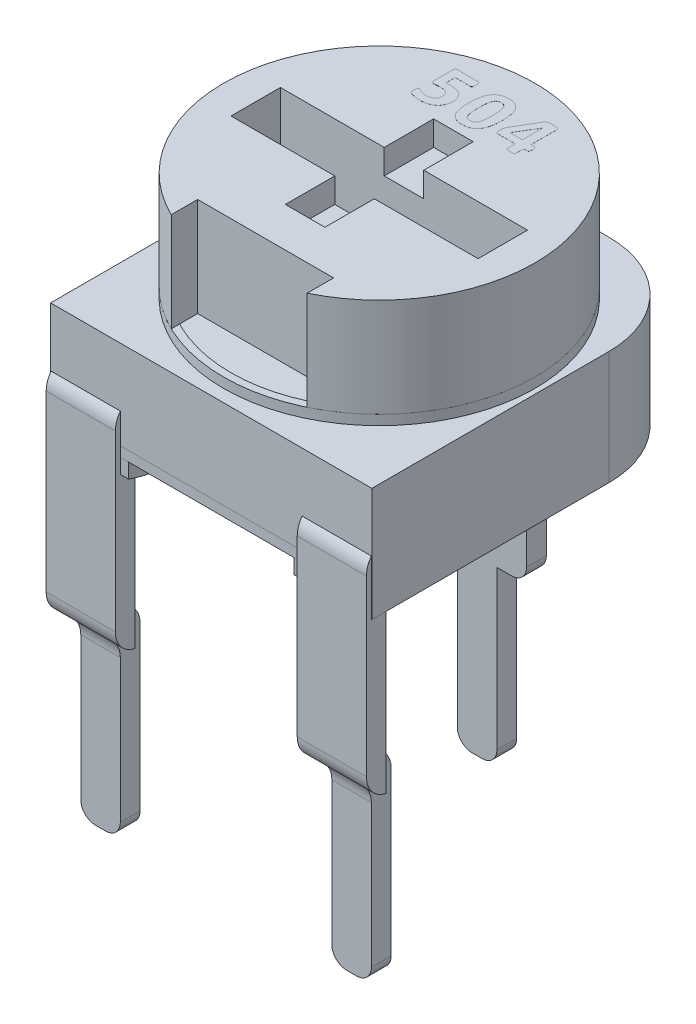
SolidWorks part; units mm, degrees
material "ABS"
ref_plane "Front Plane" through (0, 0, 0) normal (0, 0, 1) x (1, 0, 0)
ref_plane "Top Plane" through (0, 0, 0) normal (0, 1, 0) x (1, 0, 0)
ref_plane "Right Plane" through (0, 0, 0) normal (1, 0, 0) x (0, 0, -1)
sketch "Sketch1" plane through (0, 0, 0) normal (0, 1, 0) x (1, 0, 0)
  line L0 (0, 3.15) -> (0, -3.15) construction
  line L1 (0, 3.15) -> (0, 3.4) construction
  line L2 (0, -3.15) -> (0, -3.4) construction
  line L3 (-3.15, 0) -> (3.15, 0) construction
  line L4 (3.15, 0) -> (3.25, 0) construction
  line L5 (-3.15, 0) -> (-3.25, 0) construction
  line L6 (-3.25, -3.4) -> (3.25, -3.4)
  line L7 (-3.25, -3.4) -> (-3.25, 3.4)
  line L8 (-3.25, 3.4) -> (3.25, 3.4)
  line L9 (3.25, 3.4) -> (3.25, -3.4)
  circle A0 centre (0, 0) radius 3.15 construction
  dimension "D1" = 6.3
  dimension "D2" = 6.8
  dimension "D3" = 6.5
extrude "Boss-Extrude1" add sketch "Sketch1" along normal blind 2.3
sketch "Sketch2" plane through (0, 2.3, 0) normal (0, 1, 0) x (1, 0, 0)
  circle A0 centre (0, 0) radius 3.15 construction
  circle A1 centre (0, 0) radius 3.15
extrude "Boss-Extrude2" add sketch "Sketch2" along normal blind 0.2
fillet "Fillet1" radius 2 2 edges at (3.25, 1.15, -3.4) (-3.25, 1.15, -3.4)
sketch "Sketch3" plane through (0, 0, 0) normal (0, -1, 0) x (1, 0, 0)
  line L0 (0, 0) -> (0, -2.5) construction
  line L1 (-1.75, -2.5) -> (1.75, -2.5)
  line L6 (-2.25, -2) -> (-2.25, 2)
  line L7 (2.25, -2) -> (2.25, 2)
  line L8 (-2.25, 2) -> (-3, 2)
  line L9 (-3, 2) -> (-3, 3.4)
  line L10 (-3.25, 3.4) -> (3.25, 3.4) construction
  line L11 (2.25, 2) -> (3, 2)
  line L12 (3, 2) -> (3, 3.4)
  line L13 (3, 3.4) -> (-3, 3.4)
  line L14 (0, 0) -> (0, 3.4) construction
  arc A0 (-1.75, -2.5) -> (-2.25, -2) centre (-1.75, -2) cw
  arc A1 (1.75, -2.5) -> (2.25, -2) centre (1.75, -2) ccw
  point P20 (2.25, -2.5)
  dimension "D6" = 0.5
  dimension "D1" = 4.5
  dimension "D2" = 2.5
  dimension "D3" = 4.5
  dimension "D4" = 1.4
  dimension "D5" = 6
extrude "Cut-Extrude1" cut sketch "Sketch3" against normal blind 0.5
sketch "Sketch4" plane through (0, 0.5, 0) normal (0, -1, 0) x (1, 0, 0)
  line L8 (-3, 2) -> (-2.25, 2)
  line L9 (-2.25, 2) -> (-2.25, -2)
  line L10 (-1.75, -2.5) -> (1.75, -2.5)
  line L11 (2.25, -2) -> (2.25, 2)
  line L12 (2.25, 2) -> (3, 2)
  line L13 (3, 2) -> (3, 3.4)
  line L14 (3, 3.4) -> (-3, 3.4)
  line L15 (-3, 3.4) -> (-3, 2)
  line L16 (-3, 2) -> (-2.25, 2)
  line L17 (-2.25, 2) -> (-2.25, -2)
  line L18 (-1.75, -2.5) -> (1.75, -2.5)
  line L19 (2.25, -2) -> (2.25, 2)
  line L20 (2.25, 2) -> (3, 2)
  line L21 (3, 2) -> (3, 3.4)
  line L22 (3, 3.4) -> (-3, 3.4)
  line L23 (-3, 3.4) -> (-3, 2)
  arc A2 (-2.25, -2) -> (-1.75, -2.5) centre (-1.75, -2) ccw
  arc A3 (1.75, -2.5) -> (2.25, -2) centre (1.75, -2) ccw
  arc A4 (-2.25, -2) -> (-1.75, -2.5) centre (-1.75, -2) ccw
  arc A5 (1.75, -2.5) -> (2.25, -2) centre (1.75, -2) ccw
  dimension "D1" = 0
extrude "Boss-Extrude3" add sketch "Sketch4" along normal blind 0.2 separate body
sketch "Sketch5" plane through (0, 0.3, 0) normal (0, -1, 0) x (1, 0, 0)
  line L0 (0, 3.4) -> (0, 2.9) construction
  line L1 (3, 3.4) -> (-3, 3.4) construction
  line L2 (0, 2.9) -> (0, -2.18) construction
  line L3 (-2.54, 2.9) -> (2.54, 2.9) construction
  circle A0 centre (2.54, 2.9) radius 1
  circle A1 centre (-2.54, 2.9) radius 1
  circle A2 centre (0, -2.18) radius 1
  dimension "D2" = 5.08
  dimension "D4" = 2
  dimension "D1" = 0.5
  dimension "D3" = 5.08
extrude "Boss-Extrude4" add sketch "Sketch5" along normal up to surface (0.3 mm away) up to face at (0, 0, 0.1228)
sketch "Sketch6" plane through (0, 0.3, 0) normal (0, 1, 0) x (1, 0, 0)
  line L0 (-3.25, -3.4) -> (-3.25, -1)
  line L1 (-3.25, 1.4) -> (-3.25, -3.4) construction
  line L2 (-3.25, -1) -> (-4.35, -1)
  line L3 (-4.35, -1) -> (-4.35, -4.5)
  line L4 (-4.35, -4.5) -> (4.35, -4.5)
  line L5 (4.35, -4.5) -> (4.35, -1)
  line L6 (4.35, -1) -> (3.25, -1)
  line L7 (3.25, -3.4) -> (3.25, 1.4) construction
  line L8 (-3.25, -3.4) -> (3.25, -3.4)
  line L9 (3.25, -3.4) -> (3.25, -1)
  line L10 (0, 0) -> (0, -3.4) construction
  line L11 (0, -3.4) -> (0, -4.5) construction
  dimension "D1" = 3.5
extrude "Cut-Extrude2" cut sketch "Sketch6" against normal up to surface (0.3 mm away) up to face at (0, 0, -0.817)
sketch "Sketch8" plane through (0, 0.3, 0) normal (0, -1, 0) x (1, 0, 0)
  line L1 (-0.4, -1.98) -> (0.4, -1.98)
  line L2 (-0.4, -1.98) -> (-0.4, -2.38)
  line L3 (-0.4, -2.38) -> (0.4, -2.38)
  line L4 (0.4, -1.98) -> (0.4, -2.38)
  line L5 (-0.4, -1.98) -> (0.4, -2.38) construction
  line L6 (-0.4, -2.38) -> (0.4, -1.98) construction
  line L7 (-2.94, 3.1) -> (-2.14, 3.1)
  line L8 (-2.94, 3.1) -> (-2.94, 2.7)
  line L9 (-2.94, 2.7) -> (-2.14, 2.7)
  line L10 (-2.14, 3.1) -> (-2.14, 2.7)
  line L11 (-2.94, 3.1) -> (-2.14, 2.7) construction
  line L12 (-2.94, 2.7) -> (-2.14, 3.1) construction
  line L13 (2.94, 3.1) -> (2.14, 3.1)
  line L14 (2.94, 3.1) -> (2.94, 2.7)
  line L15 (2.94, 2.7) -> (2.14, 2.7)
  line L16 (2.14, 3.1) -> (2.14, 2.7)
  line L17 (2.94, 3.1) -> (2.14, 2.7) construction
  line L18 (2.94, 2.7) -> (2.14, 3.1) construction
  point P0 (0, -2.18)
  point P5 (-2.54, 2.9)
  point P11 (2.54, 2.9)
  dimension "D1" = 0.4
  dimension "D2" = 0.8
extrude "Boss-Extrude5" add sketch "Sketch8" along normal blind 7
sketch "Sketch9" plane through (0, 0.3, 0) normal (0, -1, 0) x (1, 0, 0)
  line L4 (0, -1.98) -> (0, -2.38) construction
  line L5 (0.4, -1.98) -> (-0.4, -1.98) construction
  line L6 (-0.4, -2.38) -> (0.4, -2.38) construction
  line L8 (-1, -1.98) -> (1, -1.98)
  line L9 (-1, -1.98) -> (-1, -2.38)
  line L10 (-1, -2.38) -> (1, -2.38)
  line L11 (1, -1.98) -> (1, -2.38)
  line L12 (-1, -1.98) -> (1, -2.38) construction
  line L13 (-1, -2.38) -> (1, -1.98) construction
  point P14 (0, -2.18)
  dimension "D1" = 2
extrude "Boss-Extrude6" add sketch "Sketch9" along normal blind 3.5
sketch "Sketch10" plane through (0, 0.3, 0) normal (0, -1, 0) x (1, 0, 0)
  line L0 (-2.54, 3.1) -> (-2.54, 3.5) construction
  line L1 (-2.14, 3.1) -> (-2.94, 3.1) construction
  line L2 (2.54, 3.1) -> (2.54, 3.5) construction
  line L3 (2.94, 3.1) -> (2.14, 3.1) construction
  line L4 (-2.94, 3.1) -> (-2.94, 2.7) construction
  line L5 (-3.24, 3.5) -> (-1.84, 3.5)
  line L6 (-3.24, 3.5) -> (-3.24, 3.1)
  line L7 (-3.24, 3.1) -> (-1.84, 3.1)
  line L8 (-1.84, 3.5) -> (-1.84, 3.1)
  line L10 (1.84, 3.5) -> (3.24, 3.5)
  line L11 (1.84, 3.5) -> (1.84, 3.1)
  line L12 (1.84, 3.1) -> (3.24, 3.1)
  line L13 (3.24, 3.5) -> (3.24, 3.1)
  dimension "D1" = 1.4
extrude "Boss-Extrude7" add sketch "Sketch10" along normal blind 3.5 and the other way blind 1
fillet "Fillet2" radius 0.5 2 edges at (2.54, 1.3, 3.5) (-2.54, 1.3, 3.5)
sketch "Sketch11" plane through (0, 0, 0) normal (1, 0, 0) x (0, 0, -1)
  line L0 (-3.4, 0) -> (1.4, 0) construction
  line L1 (-3.1, -2.8) -> (-2.7, -2.8)
  line L2 (-3.1, -2.8) -> (-3.1, 0)
  line L3 (-3.1, 0) -> (-2.7, 0)
  line L4 (-2.7, -2.8) -> (-2.7, 0)
  line L5 (-2.7, -6.7) -> (-2.7, 0.3) construction
  line L6 (-3.1, -2.8) -> (-3.1, -3.2) construction
extrude "Cut-Extrude3" cut sketch "Sketch11" against normal through all both and the other way through all
fillet "Fillet3" radius 0.5 4 edges at (-2.54, -2.8, 3.1) (2.54, -2.8, 3.1) (-2.54, -3.2, 3.5) (2.54, -3.2, 3.5)
fillet "Fillet4" radius 0.5 4 edges at (2.54, -2.8, 2.7) (-2.54, -2.8, 2.7) (2.54, -3.2, 3.1) (-2.54, -3.2, 3.1)
fillet "Fillet5" radius 0.3 12 edges at (-1, -3.2, -2.18) (1, -3.2, -2.18) (-0.4, -6.7, -2.18) (0.4, -6.7, -2.18) (2.14, -6.7, 2.9) (2.94, -6.7, 2.9) (-2.94, -6.7, 2.9) (-2.14, -6.7, 2.9) (-2.14, -2.7551, 3.1) (-2.94, -2.7551, 3.1) (2.14, -2.7551, 3.1) (2.94, -2.7551, 3.1)
sketch "Sketch12" plane through (0, 0.3, 0) normal (0, -1, 0) x (1, 0, 0)
  circle A0 centre (0, 0) radius 2
  circle A1 centre (0, 0) radius 1.5
  dimension "D1" = 4
  dimension "D2" = 3
extrude "Boss-Extrude8" add sketch "Sketch12" along normal blind 0.15
sketch "Sketch15" plane through (0, 2.5, 0) normal (0, 1, 0) x (1, 0, 0)
  circle A0 centre (0, 0) radius 3
  dimension "D1" = 6
extrude "Cut-Extrude4" cut sketch "Sketch15" against normal blind 0.5
sketch "Sketch14" plane through (0, 2.5, 0) normal (0, 1, 0) x (1, 0, 0)
  circle A1 centre (0, 0) radius 3.15
  circle A2 centre (0, 0) radius 3.15
  dimension "D1" = 0
extrude "Boss-Extrude9" add sketch "Sketch14" along normal blind 2 separate body
sketch "Set Angle of Knob" plane through (0, 4.5, 0) normal (0, 1, 0) x (1, 0, 0)
  line L0 (0, 0) -> (0, -3.15) construction
  line L1 (-2.5, 0) -> (2.5, 0) construction
  line L2 (-2.5, 0.5) -> (-2.5, -0.5)
  line L3 (2.5, 0.5) -> (2.5, -0.5)
  line L4 (-2.5, 0.5) -> (-0.4, 0.5)
  line L5 (-2.5, -0.5) -> (-0.4, -0.5)
  line L6 (0, 0) -> (0, -1.5) construction
  line L7 (0, 0) -> (0, 1.5) construction
  line L8 (0, 1.5) -> (0, 3.15) construction
  line L9 (0.4, 1.5) -> (-0.4, 1.5)
  line L10 (0.4, 1.5) -> (0.4, 0.5)
  line L11 (-0.4, 1.5) -> (-0.4, 0.5)
  line L12 (0.4, 0.5) -> (2.5, 0.5)
  line L13 (-0.4, -1.5) -> (0.4, -1.5)
  line L14 (-0.4, -1.5) -> (-0.4, -0.5)
  line L15 (0.4, -1.5) -> (0.4, -0.5)
  line L16 (0.4, -0.5) -> (2.5, -0.5)
  line L17 (0, -1.5) -> (0, -2.3) construction
  line L18 (-1.375, -2.3) -> (1.375, -2.3)
  line L19 (-1.375, -2.3) -> (-1.375, -3.8)
  line L20 (1.375, -2.3) -> (1.375, -3.8)
  line L21 (-1.375, -3.8) -> (1.375, -3.8)
  line L22 (-1, 0.25) -> (1, 0.25) construction
  line L23 (-1, 0.25) -> (-1, -0.25) construction
  line L24 (-1, -0.25) -> (1, -0.25) construction
  line L25 (1, -0.25) -> (1, 0.25) construction
  circle A0 centre (0, 0) radius 3.15 construction
  circle A1 centre (0, 0) radius 3.15 construction
  point P32 (0, 0.25)
  dimension "D1" = 1
  dimension "D2" = 0.8
  dimension "D3" = 1.5
  dimension "D4" = 5
  dimension "D5" = 90
  dimension "D6" = 2.75
  dimension "D7" = 1.5
  dimension "D8" = 1.8
  dimension "D9" = 0.25
  dimension "D10" = 0.25
  dimension "D11" = 2
extrude "TURN KNOB" cut sketch "Set Angle of Knob" against normal blind 2.3
sketch "Sketch17" plane through (0, 2, 0) normal (0, 1, 0) x (1, 0, 0)
  line L0 (-0.4, -1.5) -> (0.4, -1.5)
  line L1 (0.4, -1.5) -> (0.4, -0.5)
  line L2 (0.4, 1.5) -> (-0.4, 1.5)
  line L3 (-0.4, 1.5) -> (-0.4, 0.5)
  line L4 (-0.4, 0.5) -> (0.4, 0.5)
  line L5 (-0.4, -0.5) -> (0.4, -0.5)
  line L6 (-0.4, -0.5) -> (-0.4, -1.5)
  line L7 (0.4, 0.5) -> (0.4, 1.5)
extrude "Boss-Extrude10" add sketch "Sketch17" along normal blind 2
sketch "Sketch20" plane through (0, 2, 0) normal (0, 1, 0) x (1, 0, 0)
  line L0 (-1, 0.25) -> (1, 0.25) construction
  line L1 (-1, 0.25) -> (1, 0.25)
  line L2 (-1, -0.25) -> (1, -0.25) construction
  line L3 (-1, -0.25) -> (1, -0.25)
  line L4 (-1, 0.25) -> (-1, -0.25) construction
  line L5 (-1, 0.25) -> (-1, -0.25)
  line L6 (1, -0.25) -> (1, 0.25) construction
  line L7 (1, -0.25) -> (1, 0.25)
extrude "Cut-Extrude6" cut sketch "Sketch20" against normal blind 0.5
fillet "Fillet6" radius 0.2 2 edges at (1, 2, 0) (-1, 2, 0)
sketch "See Code in Properties" plane through (0, 4.5, 0) normal (0, 1, 0) x (1, 0, 0)
  line L0 (0, 1.5) -> (0, 1.7) construction
  line L1 (0.4, 1.5) -> (-0.4, 1.5) construction
  line L2 (0, 1.5) -> (0, 3.15) construction
  line L3 (-1.5, 1.7) -> (1.5, 1.7) construction
  text T0 "504" font "Calibri" height 0.9
  dimension "D1" = 0.2
  dimension "D2" = 3
extrude "Code Number" add sketch "See Code in Properties" along normal blind 0.001
